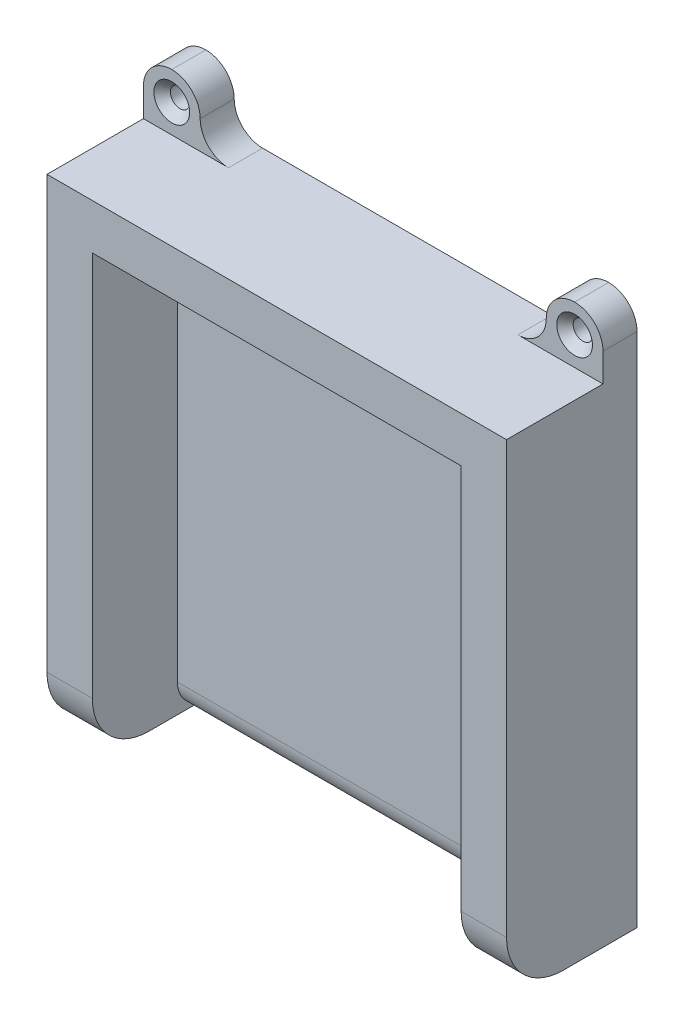
SolidWorks part; units mm, degrees
ref_plane "Plan de face" through (0, 0, 0) normal (0, 0, 1) x (1, 0, 0)
ref_plane "Plan de dessus" through (0, 0, 0) normal (0, 1, 0) x (1, 0, 0)
ref_plane "Plan de droite" through (0, 0, 0) normal (1, 0, 0) x (0, 0, -1)
sketch "Esquisse1" plane through (0, 0, 0) normal (0, 0, 1) x (1, 0, 0)
  line L1 (0, 0) -> (81, 0)
  line L2 (0, 0) -> (0, 86)
  line L3 (0, 86) -> (81, 86)
  line L4 (81, 0) -> (81, 86)
  dimension "D1" = 81
  dimension "D2" = 86
extrude "Boss.-Extru.1" add sketch "Esquisse1" along normal blind 8
sketch "Esquisse2" plane through (0, 0, 8) normal (0, 0, 1) x (1, 0, 0)
  line L1 (0, 86) -> (81, 86)
  line L3 (8, 78) -> (73, 78)
  line L4 (81, 86) -> (0, 86) construction
  line L6 (8, 78) -> (8, 0)
  line L8 (0, 86) -> (0, 0)
  line L9 (0, 0) -> (81, 0)
  line L10 (81, 0) -> (81, 86)
  line L11 (81, 86) -> (0, 86)
  line L12 (0, 86) -> (0, 0)
  line L13 (0, 0) -> (8, 0)
  line L14 (81, 0) -> (81, 86)
  line L16 (73, 78) -> (73, 0)
  line L17 (0, 0) -> (81, 0) construction
  line L19 (73, 0) -> (81, 0)
  dimension "D2" = 8
  dimension "D3" = 8
  dimension "D4" = 8
extrude "Boss.-Extru.2" add sketch "Esquisse2" along normal blind 15
fillet "Congé1" radius 10 2 edges at (77, 0, 23) (4, 0, 23)
fillet "Congé2" radius 5 1 edges at (40.5, 0, 8)
sketch "Esquisse3" plane through (0, 86, 0) normal (0, 1, 0) x (1, 0, 0)
  line L4 (40.5, 0) -> (40.5, -30.4724) construction
  line L5 (0, 0) -> (10, 0)
  line L6 (0, 0) -> (0, -6)
  line L7 (0, -6) -> (10, -6)
  line L8 (81, 0) -> (0, 0)
  line L9 (0, 0) -> (0, -23)
  line L10 (0, -23) -> (81, -23)
  line L11 (81, -23) -> (81, 0)
  line L12 (81, 0) -> (0, 0) construction
  line L13 (0, 0) -> (0, -23) construction
  line L14 (0, -23) -> (81, -23) construction
  line L15 (81, -23) -> (81, 0) construction
  line L16 (10, 0) -> (10, -6)
  line L17 (81, -6) -> (71, -6)
  line L18 (71, 0) -> (71, -6)
  line L19 (81, 0) -> (71, 0)
  line L20 (81, 0) -> (81, -6)
  dimension "D2" = 10
  dimension "D3" = 6
  dimension "D1" = 0
extrude "Boss.-Extru.3" add sketch "Esquisse3" along normal blind 10
fillet "Congé3" radius 5 6 edges at (0, 96, 3) (10, 96, 3) (10, 86, 3) (71, 86, 3) (71, 96, 3) (81, 96, 3)
sketch "Esquisse4" plane through (0, 0, 6) normal (0, 0, 1) x (1, 0, 0)
  line L0 (40.5, 86) -> (40.5, 90.0778) construction
  line L1 (81, 86) -> (0, 86) construction
  circle A0 centre (76, 91) radius 1
  circle A1 centre (5, 91) radius 1
  dimension "D1" = 2
hole_wizard "Fraisage pour vis à tête fraisée M31" positions "Esquisse5" profile "Esquisse6" countersink size "M3" standard "ISO" end condition through all
sketch "Esquisse5" plane through (0, 0, 6) normal (0, 0, 1) x (1, 0, 0)
  point P0 (76, 91)
  point P3 (5, 91)
sketch "Esquisse6" plane through (76, 91, 6) normal (1, 0, 0) x (0, -1, 0)
  line L0 (0, 0) -> (0, 6)
  line L1 (0, 6) -> (1.7, 6)
  line L2 (1.7, 6) -> (1.7, 1.45)
  line L3 (1.7, 1.45) -> (3.15, 0)
  line L5 (3.15, 0) -> (0, 0)
  line L6 (-1.7, 1.45) -> (-3.15, 0) construction
  line L11 (0, -6.35) -> (0, 107.95) construction
  dimension "Diamètre du perçage jusqu'au prochain" = 3.4
  dimension "Profondeur du perçage jusqu'au prochain" = 6
  dimension "Diamètre du fraisage entrant" = 6.3
  dimension "Angle du fraisage entrant" = 90
equation "\"epaiss_cadre\"= 8"
equation "\"D1@Esquisse1\"=\"epaiss_cadre\"*2+65"
equation "\"D1@Boss.-Extru.1\"=\"epaiss_cadre\""
equation "\"D2@Esquisse2\"=\"epaiss_cadre\""
equation "\"D3@Esquisse2\"=\"epaiss_cadre\""
equation "\"D4@Esquisse2\"=\"epaiss_cadre\""
